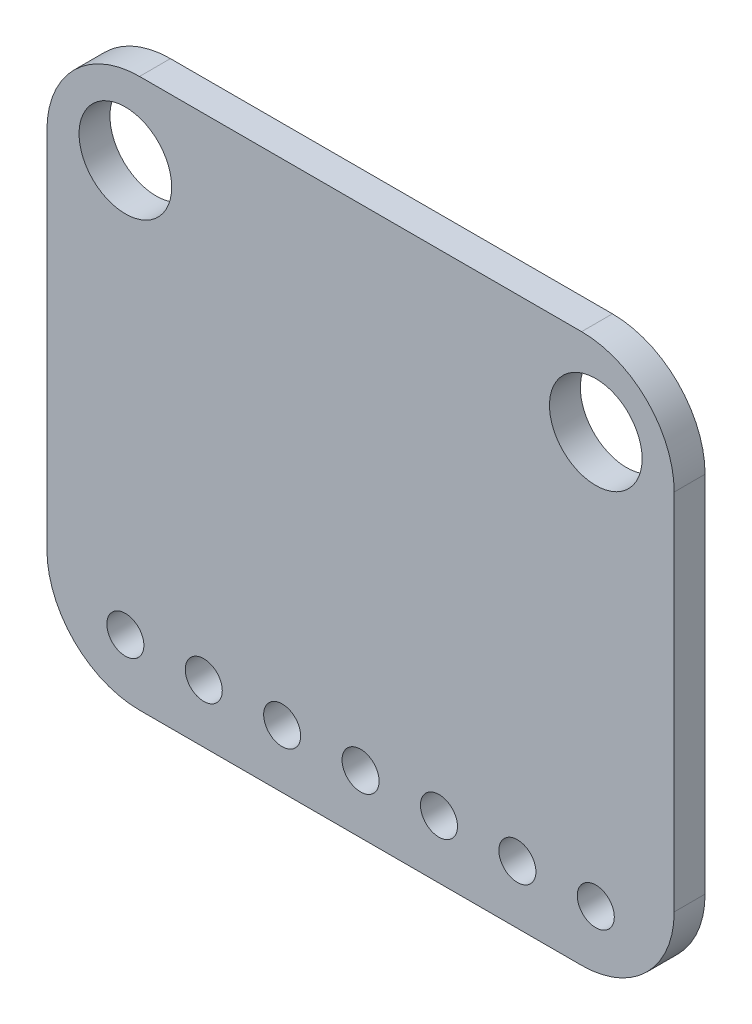
SolidWorks part; units mm, degrees
ref_plane "前视基准面" through (0, 0, 0) normal (0, 0, 1) x (1, 0, 0)
ref_plane "上视基准面" through (0, 0, 0) normal (0, 1, 0) x (1, 0, 0)
ref_plane "右视基准面" through (0, 0, 0) normal (1, 0, 0) x (0, 0, -1)
sketch "草图1" plane through (0, 0, 0) normal (0, 0, 1) x (1, 0, 0)
  line L0 (0, 18.703) -> (0, -16.1062) construction
  line L1 (-10.16, 8.89) -> (10.16, 8.89)
  line L2 (-10.16, 8.89) -> (-10.16, -8.89)
  line L3 (-10.16, -8.89) -> (10.16, -8.89)
  line L4 (10.16, 8.89) -> (10.16, -8.89)
  line L5 (-10.16, 8.89) -> (10.16, -8.89) construction
  line L6 (-10.16, -8.89) -> (10.16, 8.89) construction
  circle A0 centre (-7.62, 6.3039) radius 1.5
  circle A1 centre (7.62, 6.3039) radius 1.5
  circle A2 centre (-7.62, -7.0036) radius 0.6
  circle A3 centre (-5.08, -7.0036) radius 0.6
  circle A4 centre (-2.54, -7.0036) radius 0.6
  circle A5 centre (0, -7.0036) radius 0.6
  circle A6 centre (2.54, -7.0036) radius 0.6
  circle A7 centre (5.08, -7.0036) radius 0.6
  circle A8 centre (7.62, -7.0036) radius 0.6
  point P0 (0, 0)
  point P12 (0, -7.0036)
  point P15 (0, 0)
  point P29 (10.16, -6.9124)
  dimension "D3" = 7.62
  dimension "D6" = 3
  dimension "D7" = 1.2
  dimension "D10" = 3
  dimension "D1" = 20.32
  dimension "D2" = 17.78
  dimension "D4" = 7.62
  dimension "D8" = 1.8864
  dimension "D9" = 2.54
  dimension "D11" = 1.8864
  dimension "D12" = 2.5861
  dimension "D13" = 2.5861
  dimension "D5" = 7
extrude "凸台-拉伸1" add sketch "草图1" along normal blind 1
fillet "圆角2" radius 3 1 edges at (10.16, 8.89, 0.5) type face fillet first side face at (10.16, 0, 0.5) second side face at (0, 8.89, 0.5)
fillet "圆角3" radius 3 1 edges at (-10.16, 8.89, 0.5) type face fillet first side face at (-10.16, 0, 0.5) second side face at (-1.5, 8.89, 0.5)
fillet "圆角4" radius 3 1 edges at (-10.16, -8.89, 0.5) type face fillet first side face at (-10.16, -1.5, 0.5) second side face at (0, -8.89, 0.5)
fillet "圆角5" radius 3 1 edges at (10.16, -8.89, 0.5) type face fillet first side face at (10.16, -1.5, 0.5) second side face at (1.5, -8.89, 0.5)
sketch "草图2" plane through (0, 0, 0) normal (0, 0, 1) x (1, 0, 0)
  line L0 (7.16, 8.89) -> (-7.16, 8.89) construction
  line L1 (-2.678, 4.7704) -> (0.9021, 4.7704)
  line L2 (-2.678, 4.7704) -> (-2.678, -1.2858)
  line L3 (-2.678, -1.2858) -> (0.9021, -1.2858)
  line L4 (0.9021, 4.7704) -> (0.9021, -1.2858)
  line L5 (-2.678, 4.7704) -> (0.9021, -1.2858) construction
  line L6 (-2.678, -1.2858) -> (0.9021, 4.7704) construction
  line L7 (-10.16, 5.89) -> (-10.16, -5.89) construction
  point P0 (-0.888, 1.7423)
  dimension "D1" = 6.0562
  dimension "D2" = 3.5801
  dimension "D3" = 4.1196
  dimension "D4" = 7.482
extrude "凸台-拉伸2" add sketch "草图2" against normal blind 1 and the other way blind 1
